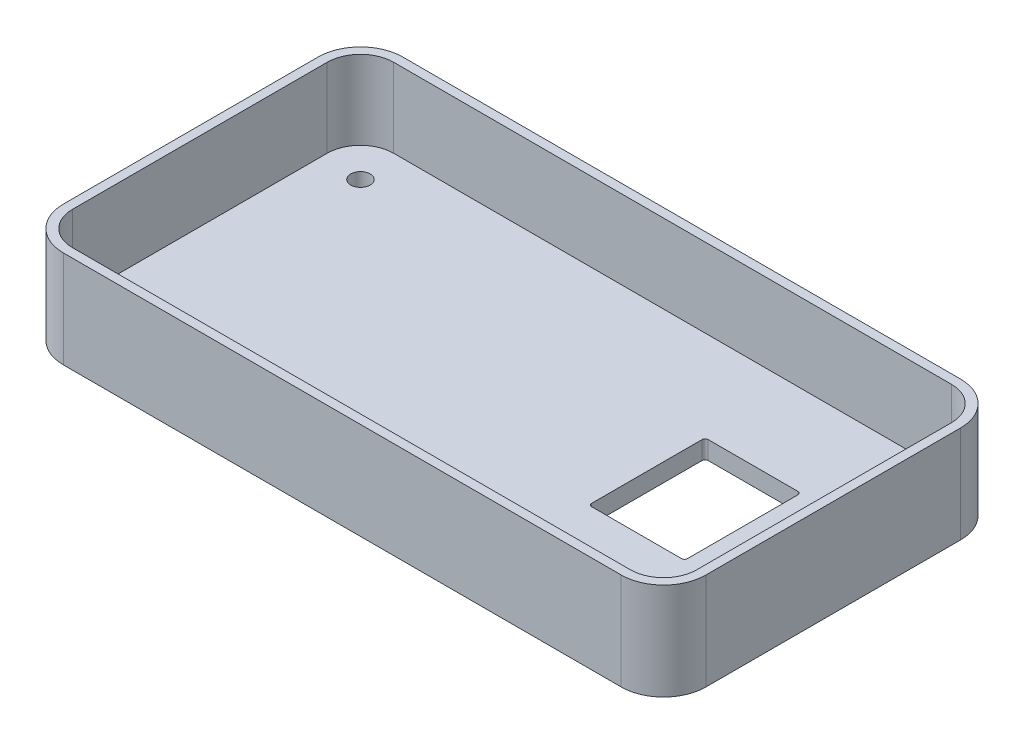
SolidWorks part; units mm, degrees
ref_plane "Front Plane" through (0, 0, 0) normal (0, 0, 1) x (1, 0, 0)
ref_plane "Top Plane" through (0, 0, 0) normal (0, 1, 0) x (1, 0, 0)
ref_plane "Right Plane" through (0, 0, 0) normal (1, 0, 0) x (0, 0, -1)
sketch "Sketch1" plane through (0, 0, 0) normal (0, 1, 0) x (1, 0, 0)
  line L0 (96.0002, 49.9874) -> (4, 49.9874)
  line L1 (0.0127, 46.0001) -> (0.0127, 4)
  line L2 (4, 0.0127) -> (96.0002, 0.0127)
  line L3 (99.9875, 4) -> (99.9875, 46.0001)
  line L4 (70.8272, 36.5271) -> (85.6272, 36.5271)
  line L5 (86.1272, 36.0271) -> (86.1272, 17.8271)
  line L6 (85.6272, 17.3271) -> (70.8272, 17.3271)
  line L7 (70.3272, 17.8271) -> (70.3272, 36.0271)
  line L9 (0.0127, 46.0001) -> (-2.9873, 46.0001)
  line L10 (4, 49.9874) -> (4, 52.9874)
  line L11 (0.0127, 4) -> (-2.9873, 4)
  line L12 (4, 0.0127) -> (4, -2.9873)
  line L13 (96.0002, 0.0127) -> (96.0002, -2.9873)
  line L14 (99.9875, 4) -> (102.9875, 4)
  line L15 (96.0002, 49.9874) -> (96.0002, 52.9874)
  line L16 (99.9875, 46.0001) -> (102.9875, 46.0001)
  line L17 (102.9875, 46.0001) -> (102.9875, 4)
  line L18 (96.0002, 52.9874) -> (4, 52.9874)
  line L19 (-2.9873, 46.0001) -> (-2.9873, 4)
  line L20 (4, -2.9873) -> (96.0002, -2.9873)
  line L21 (4, 51.4874) -> (96.0002, 51.4874)
  line L22 (101.4875, 46.0001) -> (101.4875, 4)
  line L23 (96.0002, -1.4873) -> (4, -1.4873)
  line L24 (-1.4873, 4) -> (-1.4873, 46.0001)
  circle A0 centre (5, 45.0001) radius 1.6
  circle A1 centre (5, 5) radius 1.6
  circle A2 centre (95.0002, 5) radius 1.6
  circle A3 centre (95.0002, 45.0001) radius 1.6
  arc A4 (99.9875, 46.0001) -> (96.0002, 49.9874) centre (96.0002, 46.0001) ccw
  arc A5 (96.0002, 0.0127) -> (99.9875, 4) centre (96.0002, 4) ccw
  arc A6 (0.0127, 4) -> (4, 0.0127) centre (4, 4) ccw
  arc A7 (4, 49.9874) -> (0.0127, 46.0001) centre (4, 46.0001) ccw
  arc A8 (70.3272, 36.0271) -> (70.8272, 36.5271) centre (70.8272, 36.0271) cw
  arc A9 (86.1272, 36.0271) -> (85.6272, 36.5271) centre (85.6272, 36.0271) ccw
  arc A10 (85.6272, 17.3271) -> (86.1272, 17.8271) centre (85.6272, 17.8271) ccw
  arc A11 (70.8272, 17.3271) -> (70.3272, 17.8271) centre (70.8272, 17.8271) cw
  arc A12 (96.0002, -2.9873) -> (102.9875, 4) centre (96.0002, 4) ccw
  arc A13 (-2.9873, 4) -> (4, -2.9873) centre (4, 4) ccw
  arc A14 (-2.9873, 46.0001) -> (4, 52.9874) centre (4, 46.0001) cw
  arc A15 (96.0002, 52.9874) -> (102.9875, 46.0001) centre (96.0002, 46.0001) cw
  arc A16 (-1.4873, 46.0001) -> (4, 51.4874) centre (4, 46.0001) cw
  arc A17 (96.0002, 51.4874) -> (101.4875, 46.0001) centre (96.0002, 46.0001) cw
  arc A18 (96.0002, -1.4873) -> (101.4875, 4) centre (96.0002, 4) ccw
  arc A19 (-1.4873, 4) -> (4, -1.4873) centre (4, 4) ccw
extrude "Boss-Extrude1" add sketch "Sketch1" along normal blind 3 contours L0 A7 L1 A6 L2 A5 L3 A4 A0 A1 A2 A3 L6 A11 L7 A8 L4 A9 L5 A10 | L24 L11 L1 L9 | L11 L24 L9 L19 | A19 L11 A13 L12 | L11 A19 L12 A6 | L23 L13 L2 L12 | L13 L23 L12 L20 | L13 A18 L14 A5 | A18 L13 A12 L14 | L22 L16 L3 L14 | L16 L22 L14 L17 | A17 L15 A4 L16 | L15 A17 L16 A15 | L21 L10 L0 L15 | L10 L21 L15 L18 | A16 L9 A7 L10 | L9 A16 L10 A14 region at (48.1588, 0, -24.8743) region at (50.0001, 0, -50.7374) region at (99.0413, 0, -49.0412) region at (0.9589, 0, -49.0412) region at (50.0001, 0, -52.2374) region at (99.9901, 0, -49.99) region at (100.7375, 0, -25) region at (0.0101, 0, -49.99) region at (-0.7373, 0, -25) region at (102.2375, 0, -25) region at (99.0413, 0, -0.9589) region at (-2.2373, 0, -25) region at (0.9589, 0, -0.9589) region at (99.9901, 0, -0.0101) region at (50.0001, 0, 0.7373) region at (0.0101, 0, -0.0101) region at (50.0001, 0, 2.2373)
extrude "Boss-Extrude2" add sketch "Sketch1<3>" along normal blind 16 contours L9 A16 L10 A14 | L10 L21 L15 L18 | L15 A17 L16 A15 | L16 L22 L14 L17 | A18 L13 A12 L14 | L13 L23 L12 L20 | A19 L11 A13 L12 | L11 L24 L9 L19 region at (50.0001, 0, -52.2374) region at (99.9901, 0, -49.99) region at (0.0101, 0, -49.99) region at (102.2375, 0, -25) region at (-2.2373, 0, -25) region at (99.9901, 0, -0.0101) region at (0.0101, 0, -0.0101) region at (50.0001, 0, 2.2373)
sketch "Sketch1<3>" plane through (0, 0, 0) normal (0, 1, 0) x (1, 0, 0) same geometry as "Sketch1"
